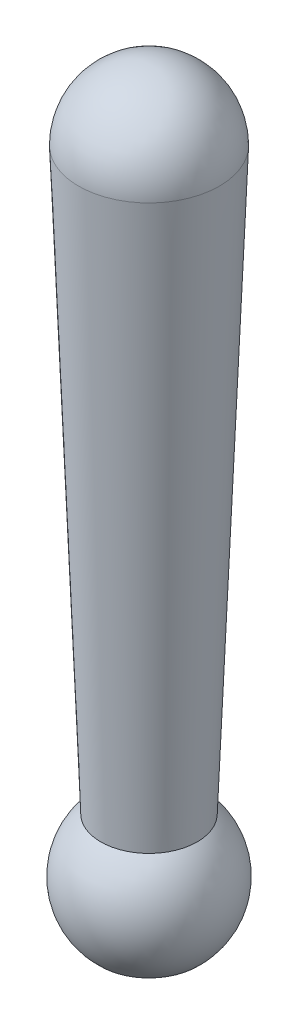
SolidWorks part; units mm, degrees
ref_plane "Front Plane" through (0, 0, 0) normal (0, 0, 1) x (1, 0, 0)
ref_plane "Top Plane" through (0, 0, 0) normal (0, 1, 0) x (1, 0, 0)
ref_plane "Right Plane" through (0, 0, 0) normal (1, 0, 0) x (0, 0, -1)
sketch "Sketch1" plane through (0, 0, 0) normal (0, 1, 0) x (1, 0, 0)
  circle A0 centre (0, 0) radius 1.46
  dimension "D1" = 2.92
ref_plane "Plane1" through (0, -12, 0) normal (0, 1, 0) x (1, 0, 0)
sketch "Sketch2" plane through (0, -12, 0) normal (0, 1, 0) x (1, 0, 0)
  circle A0 centre (0, 0) radius 1
  dimension "D1" = 2
loft "Loft1" add profiles "Sketch1", "Sketch2" connector at (-0.1739, 0, 1.4496) connector at (-0.2736, -12, 0.9619)
dome "Dome1" faces to dome 1 distance 1.46 reverse direction no elliptical dome no face at (0, 0, 1.46) parameters "D1"=1.46
sketch "Sketch3" plane through (0, 0, 0) normal (0, 0, 1) x (1, 0, 0)
  line L0 (0, -12) -> (0, -14.2361)
  line L1 (0, -12) -> (1, -12)
  line L3 (-1, -12) -> (1, -12) construction
  line L4 (0, -14.2361) -> (1, -14.2361)
  arc A0 (1, -12) -> (1, -14.2361) centre (0, -13.118) cw
  dimension "D2" = 1.5
revolve "Revolve3" add sketch "Sketch3" angle 360 about L0
ref_axis "Axis1" through (0, 2.2448, 0) along (0, -1, 0)
